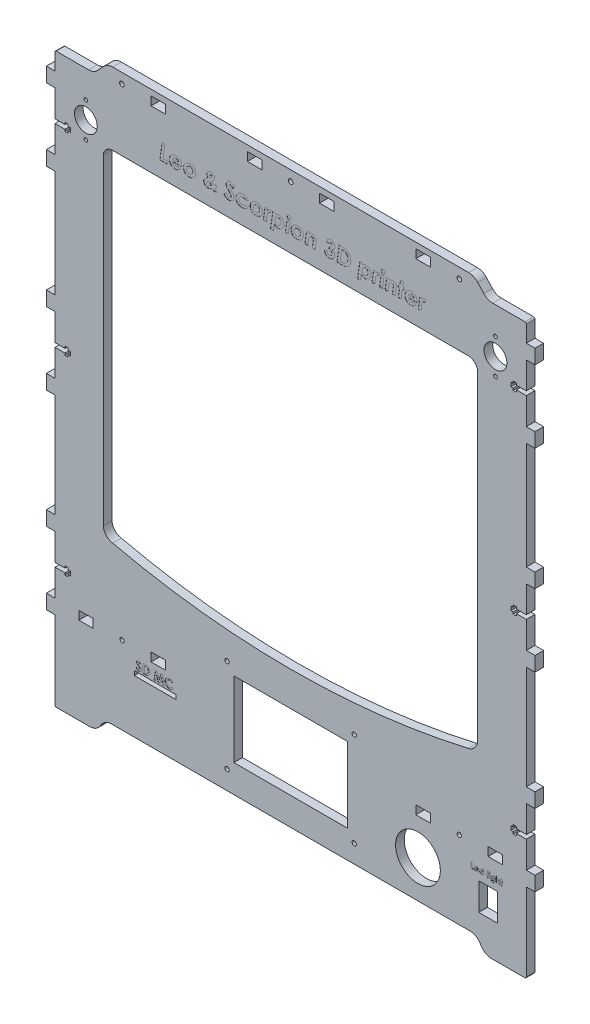
SolidWorks part; units mm, degrees
ref_plane "Спереди" through (0, 0, 0) normal (0, 0, 1) x (1, 0, 0)
ref_plane "Сверху" through (0, 0, 0) normal (0, 1, 0) x (1, 0, 0)
ref_plane "Справа" through (0, 0, 0) normal (1, 0, 0) x (0, 0, -1)
sketch "Эскиз1" plane through (0, 0, 0) normal (0, 0, 1) x (1, 0, 0)
  line L0 (-95.8892, 197.3491) -> (-85.8892, 197.3491)
  line L1 (-85.8892, 197.3491) -> (-85.8892, 191.3491)
  line L2 (-85.8892, 191.3491) -> (-95.8892, 191.3491)
  line L3 (-95.8892, 191.3491) -> (-95.8892, 197.3491)
  line L4 (97.3908, 191.3491) -> (87.3908, 191.3491)
  line L5 (87.3908, 191.3491) -> (87.3908, 197.3491)
  line L6 (87.3908, 197.3491) -> (97.3908, 197.3491)
  line L7 (97.3908, 197.3491) -> (97.3908, 191.3491)
  line L8 (97.3654, -141.9477) -> (87.3654, -141.9477)
  line L9 (87.3654, -141.9477) -> (87.3654, -135.9477)
  line L10 (87.3654, -135.9477) -> (97.3654, -135.9477)
  line L11 (97.3654, -135.9477) -> (97.3654, -141.9477)
  line L12 (147.3854, -141.9477) -> (137.3854, -141.9477)
  line L13 (137.3854, -141.9477) -> (137.3854, -135.9477)
  line L14 (137.3854, -135.9477) -> (147.3854, -135.9477)
  line L15 (147.3854, -135.9477) -> (147.3854, -141.9477)
  line L16 (-135.8946, -141.9477) -> (-145.8946, -141.9477)
  line L17 (-145.8946, -141.9477) -> (-145.8946, -135.9477)
  line L18 (-145.8946, -135.9477) -> (-135.8946, -135.9477)
  line L19 (-135.8946, -135.9477) -> (-135.8946, -141.9477)
  line L20 (-85.8746, -141.9477) -> (-95.8746, -141.9477)
  line L21 (-95.8746, -141.9477) -> (-95.8746, -135.9477)
  line L22 (-95.8746, -135.9477) -> (-85.8746, -135.9477)
  line L23 (-85.8746, -135.9477) -> (-85.8746, -141.9477)
  line L24 (-19.2392, 191.3491) -> (-29.2392, 191.3491)
  line L25 (-29.2392, 191.3491) -> (-29.2392, 197.3491)
  line L26 (-29.2392, 197.3491) -> (-19.2392, 197.3491)
  line L27 (-19.2392, 197.3491) -> (-19.2392, 191.3491)
  line L28 (30.7408, 191.3491) -> (20.7408, 191.3491)
  line L29 (20.7408, 191.3491) -> (20.7408, 197.3491)
  line L30 (20.7408, 197.3491) -> (30.7408, 197.3491)
  line L31 (30.7408, 197.3491) -> (30.7408, 191.3491)
  line L32 (-122.3991, 151.3491) -> (123.6241, 151.3491)
  line L33 (40.0454, -173.6357) -> (40.0454, -121.6361)
  line L34 (40.0454, -121.6361) -> (-38.5546, -121.6361)
  line L35 (-38.5546, -121.6361) -> (-38.5546, -173.6357)
  line L36 (-38.5546, -173.6357) -> (40.0454, -173.6357)
  line L37 (143.9388, -159.6762) -> (143.9388, -178.6762)
  line L38 (143.9388, -178.6762) -> (130.9388, -178.6762)
  line L39 (130.9388, -178.6762) -> (130.9388, -159.6762)
  line L40 (130.9388, -159.6762) -> (143.9388, -159.6762)
  line L41 (-162.3492, -146.9309) -> (-168.3546, -146.9309)
  line L42 (-168.3546, -146.9309) -> (-168.3546, -136.9309)
  line L43 (-168.3546, -136.9309) -> (-162.3546, -136.9309)
  line L44 (-162.3546, -136.9309) -> (-162.3546, -118.3209)
  line L45 (-162.3546, -96.9409) -> (-168.3546, -96.9409)
  line L46 (-168.3546, -96.9409) -> (-168.3546, -86.9409)
  line L47 (-168.3546, -86.9409) -> (-162.3546, -86.9409)
  line L48 (-162.3546, -86.9409) -> (-162.3546, -15.2109)
  line L49 (-162.3546, -15.2109) -> (-168.3546, -15.2109)
  line L50 (-162.3546, 34.7891) -> (-168.3546, 34.7891)
  line L51 (-168.3546, -5.2109) -> (-162.3546, -5.2109)
  line L52 (-168.3546, 44.7891) -> (-162.3546, 44.7891)
  line L56 (-162.3546, 128.9491) -> (-162.3546, 147.5491)
  line L57 (-162.3492, 168.9491) -> (-168.3492, 168.9491)
  line L58 (-168.3492, 168.9491) -> (-168.3492, 178.9491)
  line L59 (-168.3492, 178.9491) -> (-162.3492, 178.9491)
  line L60 (-162.3492, 178.9491) -> (-162.3492, 190.3491)
  line L61 (-162.3492, -200.9709) -> (-162.3492, -146.9309)
  line L62 (163.8454, -146.9309) -> (169.8454, -146.9309)
  line L63 (169.8454, -146.9309) -> (169.8454, -136.9309)
  line L64 (169.8454, -136.9309) -> (163.8513, -136.9309)
  line L65 (163.8513, -136.9309) -> (163.8513, -118.3209)
  line L66 (163.9392, -96.9409) -> (169.8512, -96.9409)
  line L67 (169.8512, -96.9409) -> (169.8512, -86.9409)
  line L68 (169.8512, -86.9409) -> (163.8512, -86.9409)
  line L69 (163.8512, -86.9409) -> (163.8512, -15.2109)
  line L70 (163.8512, -15.2109) -> (169.8512, -15.2109)
  line L71 (163.8512, 34.7891) -> (169.8512, 34.7891)
  line L72 (169.8512, -5.2109) -> (163.8512, -5.2109)
  line L73 (169.8512, 44.7891) -> (163.8512, 44.7891)
  line L74 (163.8512, 118.9491) -> (169.8512, 118.9491)
  line L75 (169.8512, 118.9491) -> (169.8512, 128.9491)
  line L76 (169.8512, 128.9491) -> (163.8512, 128.9491)
  line L77 (163.8512, 128.9491) -> (163.8512, 147.5491)
  line L78 (163.8508, 168.9491) -> (169.8508, 168.9491)
  line L79 (169.8508, 168.9491) -> (169.8508, 178.9491)
  line L80 (169.8508, 178.9491) -> (163.8508, 178.9491)
  line L81 (163.8508, 178.9491) -> (163.8508, 190.3491)
  line L82 (156.9388, 150.3491) -> (156.9388, 151.7492)
  line L83 (163.9392, -115.5209) -> (156.9392, -115.5209)
  line L84 (156.9392, -114.1224) -> (154.7382, -114.1224)
  line L85 (156.9399, -118.3209) -> (163.8513, -118.3209)
  line L86 (153.2384, -118.3222) -> (154.7405, -118.3222)
  line L87 (-155.4441, 11.989) -> (-153.2432, 11.989)
  line L88 (154.7382, -114.1224) -> (154.7382, -115.5222)
  line L89 (154.7391, 16.1893) -> (153.24, 16.1893)
  line L90 (153.2384, -115.5222) -> (153.2384, -118.3222)
  line L91 (-155.4426, -119.721) -> (-153.2418, -119.721)
  line L92 (163.8508, 150.3491) -> (156.9388, 150.3491)
  line L93 (156.9399, -119.7231) -> (156.9399, -118.3209)
  line L94 (156.9392, -115.5209) -> (156.9392, -114.1224)
  line L95 (154.7382, -115.5222) -> (153.2384, -115.5222)
  line L96 (154.741, 147.5502) -> (154.741, 146.1493)
  line L97 (-155.4451, -114.1209) -> (-155.4451, -115.5209)
  line L98 (154.7415, 13.3902) -> (154.7415, 11.9893)
  line L99 (-162.3546, 147.5491) -> (-155.4441, 147.5491)
  line L100 (-155.4441, 147.5491) -> (-155.4441, 146.149)
  line L101 (-155.4398, 150.3491) -> (-162.3492, 150.3491)
  line L102 (-153.2398, 150.3482) -> (-153.2398, 151.7491)
  line L103 (154.7405, -118.3222) -> (154.7405, -119.7231)
  line L104 (-155.4451, -115.5209) -> (-162.3546, -115.5209)
  line L105 (154.741, 151.7492) -> (154.741, 150.3493)
  line L106 (156.9417, 146.1493) -> (156.9417, 147.5491)
  line L107 (-153.2432, 13.3622) -> (-151.7428, 13.3622)
  line L108 (-155.4426, -118.3209) -> (-155.4426, -119.721)
  line L109 (153.241, 150.3493) -> (153.241, 147.5502)
  line L110 (-153.2451, 17.5891) -> (-155.4451, 17.5891)
  line L111 (-162.3546, 13.3891) -> (-155.4441, 13.3891)
  line L112 (154.741, 146.1493) -> (156.9417, 146.1493)
  line L113 (153.241, 147.5502) -> (154.741, 147.5502)
  line L114 (-153.2433, 147.5489) -> (-151.7375, 147.5489)
  line L115 (-151.7428, 13.3622) -> (-151.7428, 16.1885)
  line L116 (163.8512, 16.1891) -> (156.9392, 16.1891)
  line L117 (154.7391, 17.5621) -> (154.7391, 16.1893)
  line L118 (154.741, 150.3493) -> (153.241, 150.3493)
  line L119 (154.7415, 11.9893) -> (156.9417, 11.9893)
  line L120 (-153.2451, -114.1209) -> (-155.4451, -114.1209)
  line L121 (-151.7436, -118.3211) -> (-151.7436, -115.5218)
  line L122 (-153.2418, -118.3211) -> (-151.7436, -118.3211)
  line L123 (-153.2432, 11.989) -> (-153.2432, 13.3622)
  line L124 (156.9417, 13.3891) -> (163.8512, 13.3891)
  line L125 (-162.3546, -118.3209) -> (-155.4426, -118.3209)
  line L126 (153.24, 16.1893) -> (153.24, 13.3902)
  line L127 (-153.2451, -115.5218) -> (-153.2451, -114.1209)
  line L128 (-151.7428, 16.1885) -> (-153.2451, 16.1885)
  line L129 (-155.4441, 146.149) -> (-153.2433, 146.149)
  line L130 (-153.2418, -119.721) -> (-153.2418, -118.3211)
  line L131 (-155.4398, 151.7491) -> (-155.4398, 150.3491)
  line L132 (-151.7436, -115.5218) -> (-153.2451, -115.5218)
  line L133 (-153.2433, 146.149) -> (-153.2433, 147.5489)
  line L134 (153.24, 13.3902) -> (154.7415, 13.3902)
  line L135 (156.9388, 151.7492) -> (154.741, 151.7492)
  line L136 (-151.7375, 147.5489) -> (-151.738, 150.3482)
  line L137 (156.9417, 147.5491) -> (163.8512, 147.5491)
  line L138 (-155.4451, 16.1891) -> (-162.3546, 16.1891)
  line L139 (156.9417, 11.9893) -> (156.9417, 13.3891)
  line L140 (-155.4451, 17.5891) -> (-155.4451, 16.1891)
  line L141 (154.7405, -119.7231) -> (156.9399, -119.7231)
  line L142 (-153.2398, 151.7491) -> (-155.4398, 151.7491)
  line L143 (156.9392, 17.5621) -> (154.7391, 17.5621)
  line L144 (-151.738, 150.3482) -> (-153.2398, 150.3482)
  line L145 (-162.3546, -115.5209) -> (-162.3546, -96.9409)
  line L146 (-162.3492, 150.3491) -> (-162.3492, 168.9491)
  line L147 (163.9392, -115.5209) -> (163.9392, -96.9409)
  line L148 (163.8508, 150.3491) -> (163.8508, 168.9491)
  line L149 (-139.0924, 191.3491) -> (-161.5253, 191.3491)
  line L150 (-128.7242, 198.5879) -> (-132.8221, 194.1104)
  line L151 (123.9554, 201.3491) -> (-122.4539, 201.3491)
  line L152 (130.2257, 198.5879) -> (134.3236, 194.1104)
  line L153 (140.5939, 191.3491) -> (162.8508, 191.3491)
  line L154 (-131.8015, -198.9146) -> (-129.7448, -195.8949)
  line L155 (162.7628, -201.9477) -> (139.7264, -201.9477)
  line L156 (133.303, -198.9146) -> (131.2463, -195.8949)
  line L157 (-161.4373, -201.9509) -> (-138.3129, -201.9509)
  line L158 (-123.2334, -192.8586) -> (124.7349, -192.8586)
  line L159 (163.8454, -200.9731) -> (163.8454, -146.9309)
  line L160 (-162.3546, 13.3891) -> (-162.3546, -5.2109)
  line L161 (-168.3546, -15.2109) -> (-168.3546, -5.2109)
  line L162 (-168.3546, 34.7891) -> (-168.3546, 44.7891)
  line L163 (-162.3546, 44.7891) -> (-162.3546, 118.9491)
  line L164 (163.8512, 13.3891) -> (163.8512, -5.2109)
  line L165 (169.8512, -15.2109) -> (169.8512, -5.2109)
  line L166 (169.8512, 34.7891) -> (169.8512, 44.7891)
  line L167 (163.8512, 44.7891) -> (163.8512, 118.9491)
  line L168 (-155.4441, 13.3891) -> (-155.4441, 11.989)
  line L169 (-153.2451, 16.1885) -> (-153.2451, 17.5891)
  line L170 (156.9392, 16.1891) -> (156.9392, 17.5621)
  line L171 (-162.3546, 34.7891) -> (-162.3546, 16.1891)
  line L172 (163.8512, 34.7891) -> (163.8512, 16.1891)
  line L173 (-107.5042, -155.9271) -> (-107.5042, -152.9271)
  line L174 (-107.5042, -152.9271) -> (-78.5042, -152.9271)
  line L175 (-78.5042, -152.9271) -> (-78.5042, -155.9271)
  line L176 (-78.5042, -155.9271) -> (-107.5042, -155.9271)
  line L177 (-162.3546, 128.9491) -> (-168.3546, 128.9491)
  line L178 (-162.3546, 118.9491) -> (-168.3546, 118.9491)
  line L179 (-168.3546, 118.9491) -> (-168.3546, 128.9491)
  line L180 (-155.4426, -141.9477) -> (156.9399, -141.9477) construction
  line L181 (-140.9992, 144.3414) -> (-140.9992, 175.9536) construction
  line L182 (142.5008, 178.9491) -> (142.5008, 143.1493) construction
  line L183 (130.1588, 145.3729) -> (130.1254, -76.9742)
  line L184 (-128.9341, 145.3729) -> (-128.9472, -76.974)
  arc A0 (-122.4711, -84.0153) -> (123.6489, -84.0153) centre (0.5889, 449.8336) ccw
  circle A3 centre (44.7454, -115.1361) radius 1.5
  circle A4 centre (44.7454, -180.3857) radius 1.5
  circle A5 centre (-43.2546, -179.8825) radius 1.5
  circle A6 centre (-43.2546, -115.1361) radius 1.5
  circle A7 centre (88.8454, -166.9477) radius 15.5
  arc A8 (130.1588, 145.3729) -> (123.6241, 151.3491) centre (123.6241, 144.7884) ccw
  arc A9 (-122.3991, 151.3491) -> (-128.9341, 145.3729) centre (-122.472, 144.8677) ccw
  arc A10 (-128.9472, -76.974) -> (-122.4711, -84.0153) centre (-121.245, -76.3888) ccw
  arc A11 (123.6489, -84.0153) -> (130.1254, -76.9742) centre (121.7477, -75.7674) ccw
  circle A12 centre (0.7508, 194.3491) radius 1.6
  circle A13 centre (-116.0492, 194.3491) radius 1.6
  arc A14 (134.3236, 194.1104) -> (140.5939, 191.3491) centre (140.5939, 199.8491) ccw
  arc A15 (-161.5253, 191.3491) -> (-162.3492, 190.3491) centre (-161.4373, 190.4372) ccw
  arc A16 (-139.0924, 191.3491) -> (-132.8221, 194.1104) centre (-139.0924, 199.8491) ccw
  arc A17 (-122.4539, 201.3491) -> (-128.7242, 198.5879) centre (-122.4539, 192.8491) ccw
  circle A18 centre (117.5508, 194.3491) radius 1.6
  arc A19 (130.2257, 198.5879) -> (123.9554, 201.3491) centre (123.9554, 192.8491) ccw
  arc A20 (163.8508, 190.3491) -> (162.8508, 191.3491) centre (162.8508, 190.3491) ccw
  arc A21 (-123.2334, -192.8586) -> (-129.7448, -195.8949) centre (-123.2334, -201.3586) ccw
  arc A22 (-138.3129, -201.9509) -> (-131.8015, -198.9146) centre (-138.3129, -193.4509) ccw
  arc A23 (131.2463, -195.8949) -> (124.7349, -192.8586) centre (124.7349, -201.3586) ccw
  arc A24 (133.303, -198.9146) -> (139.7264, -201.9477) centre (139.7677, -193.542) ccw
  arc A25 (-162.3492, -200.9709) -> (-161.4373, -201.9509) centre (-161.3926, -200.9949) ccw
  arc A26 (162.7628, -201.9477) -> (163.8454, -200.9731) centre (162.8028, -200.9035) ccw
  circle A27 centre (-140.9992, 160.3491) radius 7.9
  circle A28 centre (142.5008, 160.3491) radius 7.9
  circle A29 centre (-115.9946, -138.9477) radius 1.5
  circle A30 centre (117.4854, -138.9477) radius 1.5
  circle A31 centre (-140.9992, 172.3491) radius 1.25
  circle A32 centre (-140.9992, 148.3491) radius 1.25
  circle A33 centre (142.5008, 172.3491) radius 1.25
  circle A34 centre (142.5008, 148.3491) radius 1.25
  point P239 (87.3908, 194.3491)
  point P241 (-162.3492, 184.6491)
  point P256 (0, 0)
  dimension "D11" = 15.8
  dimension "D12" = 15.8
  dimension "D53" = 31
  dimension "D88" = 283.5
  dimension "D115" = 2.5
  dimension "D113" = 2.5
  dimension "D116" = 12
  dimension "D117" = 12
  dimension "D118" = 2.5
  dimension "D119" = 2.5
  dimension "D120" = 12
  dimension "D121" = 12
  dimension "D1" = 10
  dimension "D2" = 12.4
  dimension "D3" = 12.4
  dimension "D4" = 10
  dimension "D5" = 18.6
  dimension "D6" = 2.8
  dimension "D7" = 18.6
  dimension "D8" = 10
  dimension "D9" = 10
  dimension "D10" = 10
  dimension "D13" = 6
  dimension "D14" = 18.6
  dimension "D15" = 18.6
  dimension "D16" = 10
  dimension "D17" = 74.16
  dimension "D18" = 74.16
  dimension "D19" = 10
  dimension "D20" = 10
  dimension "D21" = 18.6
  dimension "D22" = 18.6
  dimension "D23" = 18.6
  dimension "D24" = 18.6
  dimension "D25" = 10
  dimension "D26" = 10
  dimension "D27" = 71.73
  dimension "D28" = 71.73
  dimension "D29" = 10
  dimension "D30" = 10
  dimension "D31" = 18.58
  dimension "D32" = 18.58
  dimension "D33" = 18.61
  dimension "D34" = 18.61
  dimension "D35" = 10
  dimension "D36" = 10
  dimension "D37" = 54.04
  dimension "D38" = 54.0422
  dimension "D39" = 403.2968
  dimension "D40" = 2.8
  dimension "D41" = 2.8
  dimension "D42" = 2.8
  dimension "D43" = 2.8
  dimension "D44" = 403.3
  dimension "D45" = 10
  dimension "D46" = 10
  dimension "D47" = 10
  dimension "D48" = 169.1
  dimension "D49" = 10
  dimension "D50" = 10
  dimension "D51" = 10
  dimension "D52" = 10
  dimension "D54" = 338.2
  dimension "D55" = 169.1
  dimension "D56" = 10
  dimension "D57" = 52.3
  dimension "D58" = 52.3
  dimension "D59" = 72.46
  dimension "D60" = 72.46
  dimension "D61" = 56.65
  dimension "D62" = 56.65
  dimension "D63" = 19.99
  dimension "D64" = 19.99
  dimension "D65" = 21.35
  dimension "D66" = 21.35
  dimension "D67" = 22.46
  dimension "D68" = 22.46
  dimension "D69" = 19.9
  dimension "D70" = 19.9
  dimension "D71" = 20.12
  dimension "D72" = 20.12
  dimension "D73" = 47.32
  dimension "D74" = 78.6
  dimension "D75" = 47.32
  dimension "D76" = 4.7
  dimension "D77" = 4.7
  dimension "D78" = 4.7
  dimension "D79" = 4.7
  dimension "D80" = 6.5
  dimension "D81" = 6.5
  dimension "D82" = 6
  dimension "D83" = 60
  dimension "D84" = 55.02
  dimension "D85" = 6
  dimension "D86" = 29
  dimension "D87" = 3
  dimension "D89" = 4
  dimension "D90" = 7
  dimension "D91" = 6
  dimension "D92" = 4
  dimension "D93" = 6
  dimension "D94" = 7
  dimension "D95" = 4
  dimension "D96" = 6
  dimension "D97" = 4
  dimension "D98" = 2.8
  dimension "D99" = 7
  dimension "D100" = 31
  dimension "D101" = 31
  dimension "D102" = 166.56
  dimension "D103" = 131.73
  dimension "D104" = 51.9996
  dimension "D105" = 6
  dimension "D106" = 3
  dimension "D107" = 6
  dimension "D108" = 3
  dimension "D109" = 6
  dimension "D110" = 25
  dimension "D111" = 6
  dimension "D112" = 75
  dimension "D114" = 326.2
  dimension "D122" = 50
  dimension "D123" = 13
  dimension "D124" = 19
extrude "Бобышка-Вытянуть2" add sketch "Эскиз1" along normal blind 6 contours A5 | A4 | A3 | A13 | A12 | A7 | A6 | L32 A8 L183 A11 A0 A10 L184 A9 | A18 | A30 | A29 | A28 | A27 | L4 L5 L6 L7 | L0 L1 L2 L3 | L20 L21 L22 L23 | L16 L17 L18 L19 | L12 L13 L14 L15 | L8 L9 L10 L11 | L37 L38 L39 L40 | L33 L34 L35 L36 | L28 L29 L30 L31 | L24 L25 L26 L27 | L41 L42 L43 L44 L125 L108 L91 L130 L122 L121 L132 L127 L120 L97 L104 L145 L45 L46 L47 L48 L49 L161 L51 L160 L111 L168 L87 L123 L107 L115 L128 L169 L110 L140 L138 L171 L50 L162 L52 L163 L178 L179 L177 L56 L99 L100 L129 L133 L114 L136 L144 L102 L142 L131 L101 L146 L57 L58 L59 L60 A15 L149 A16 L150 A17 L151 A19 L152 A14 L153 A20 L81 L80 L79 L78 L148 L92 L82 L135 L105 L118 L109 L113 L96 L112 L106 L137 L77 L76 L75 L74 L167 L73 L166 L71 L172 L116 L170 L143 L117 L89 L126 L134 L98 L119 L139 L124 L164 L72 L165 L70 L69 L68 L67 L66 L147 L83 L94 L84 L88 L95 L90 L86 L103 L141 L93 L85 L65 L64 L63 L62 L159 A26 L155 A24 L156 A23 L158 A21 L154 A22 L157 A25 L61 | L173 L174 L175 L176 | A32 | A31 | A33 | A34
sketch "Эскиз2" plane through (0, 0, 6) normal (0, 0, 1) x (1, 0, 0)
  line L0 (-90.3522, 162.0224) -> (97.3655, 162.0224) construction
  text T0 "<b><i>Leo & Scorpion 3D printer</i></b>" font "Century Gothic" height 11
  point P2 (-95.8892, 162.3071)
  point P3 (89.3591, 162.576)
  point P5 (-86.6766, 162.5475)
  point P6 (97.3655, 162.0224)
  point P7 (-90.3522, 162.0224)
extrude "Вырез-Вытянуть1" cut sketch "Эскиз2" against normal blind 0.1
sketch "Эскиз3" plane through (0, 0, 6) normal (0, 0, 1) x (1, 0, 0)
  line L0 (-107.2394, -151.5718) -> (-78.6482, -151.5718) construction
  text T0 "<b>SD MC</b>" font "Century Gothic" height 6
extrude "Вырез-Вытянуть2" cut sketch "Эскиз3" against normal blind 0.1
sketch "Эскиз4" plane through (0, 0, 6) normal (0, 0, 1) x (1, 0, 0)
  line L0 (124.0715, -154.8104) -> (149.0052, -154.8104) construction
  text T0 "<b>Led light</b>" font "Century Gothic" height 4
extrude "Вырез-Вытянуть3" cut sketch "Эскиз4" against normal blind 0.1
